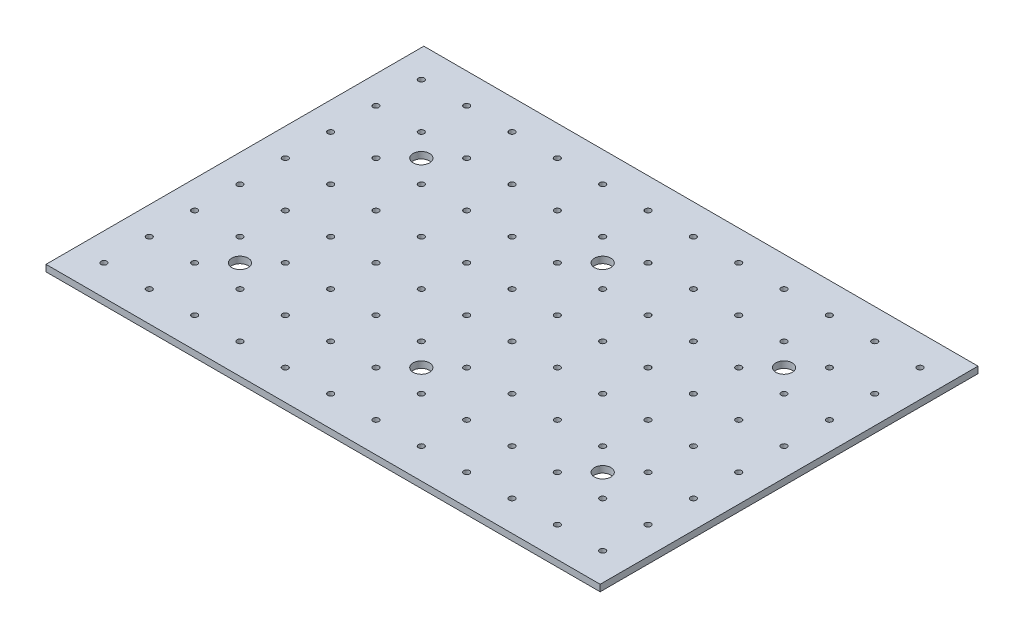
SolidWorks part; units mm, degrees
ref_plane "Front Plane" through (0, 0, 0) normal (0, 0, 1) x (1, 0, 0)
ref_plane "Top Plane" through (0, 0, 0) normal (0, 1, 0) x (1, 0, 0)
ref_plane "Right Plane" through (0, 0, 0) normal (1, 0, 0) x (0, 0, -1)
sketch "Sketch1" plane through (0, 0, 0) normal (0, 1, 0) x (1, 0, 0)
  line L1 (55, -37.5) -> (-55, -37.5)
  line L2 (55, -37.5) -> (55, 37.5)
  line L3 (55, 37.5) -> (-55, 37.5)
  line L4 (-55, -37.5) -> (-55, 37.5)
  line L5 (55, -37.5) -> (-55, 37.5) construction
  line L6 (55, 37.5) -> (-55, -37.5) construction
  point P0 (0, 0)
  dimension "D1" = 110
  dimension "D2" = 75
extrude "Boss-Extrude1" add sketch "Sketch1" along normal mid plane 1.3
sketch "Sketch2" plane through (0, 0, 0) normal (0, 1, 0) x (1, 0, 0)
  line L0 (0, -0.715) -> (0, 0.715) construction
  line L1 (-0.715, 0) -> (0.715, 0) construction
  circle A0 centre (-4.5, 4.5) radius 0.575
  dimension "D1" = 1.15
  dimension "D2" = 4.5
  dimension "D3" = 4.5
extrude "Cut-Extrude2" cut sketch "Sketch2" along normal through all and the other way through all
ref_axis "Axis1" through (-60.5, 0, 0) along (1, 0, 0)
ref_axis "Axis2" through (0, 0, 41.25) along (0, 0, -1)
pattern_linear "LPattern1" count 6 spacing 9 along (-1, 0, 0) count 4 spacing 9 along (0, 0, -1) of "Cut-Extrude2"
mirror "Mirror1" about plane through (0, 0, 0) normal (0, 0, 1) of "LPattern1", "Cut-Extrude2"
mirror "Mirror2" about plane through (0, 0, 0) normal (1, 0, 0) of "Cut-Extrude2", "Mirror1", "LPattern1"
hole_wizard "#4 Clearance Hole1" positions "Sketch3" profile "Sketch4" hole size "#4" standard "ANSI Inch" end condition through all
sketch "Sketch3" plane through (0, 0.65, 0) normal (0, 1, 0) x (1, 0, 0)
  line L1 (36, -18) -> (-36, -18) construction
  line L2 (36, -18) -> (36, 18) construction
  line L3 (36, 18) -> (-36, 18) construction
  line L4 (-36, -18) -> (-36, 18) construction
  line L5 (36, -18) -> (-36, 18) construction
  line L6 (36, 18) -> (-36, -18) construction
  line L7 (-0.715, 0) -> (0.715, 0) construction
  line L8 (0, -0.715) -> (0, 0.715) construction
  point P2 (-36, 18)
  point P139 (36, -18)
  point P140 (36, 18)
  point P141 (-36, -18)
  point P149 (0, 18)
  point P151 (0, -18)
  dimension "D1" = 18
  dimension "D2" = 36
sketch "Sketch4" plane through (-36, 0.65, -18) normal (1, 0, 0) x (0, 0, 1)
  line L0 (0, 0) -> (0, 1.3)
  line L1 (0, 1.3) -> (1.6319, 1.3)
  line L2 (1.6319, 1.3) -> (1.6319, 0)
  line L5 (1.6319, 0) -> (0, 0)
  line L11 (0, -6.35) -> (0, 107.95) construction
  dimension "Thru Hole Dia." = 3.2639
  dimension "Thru Hole Depth" = 1.3
